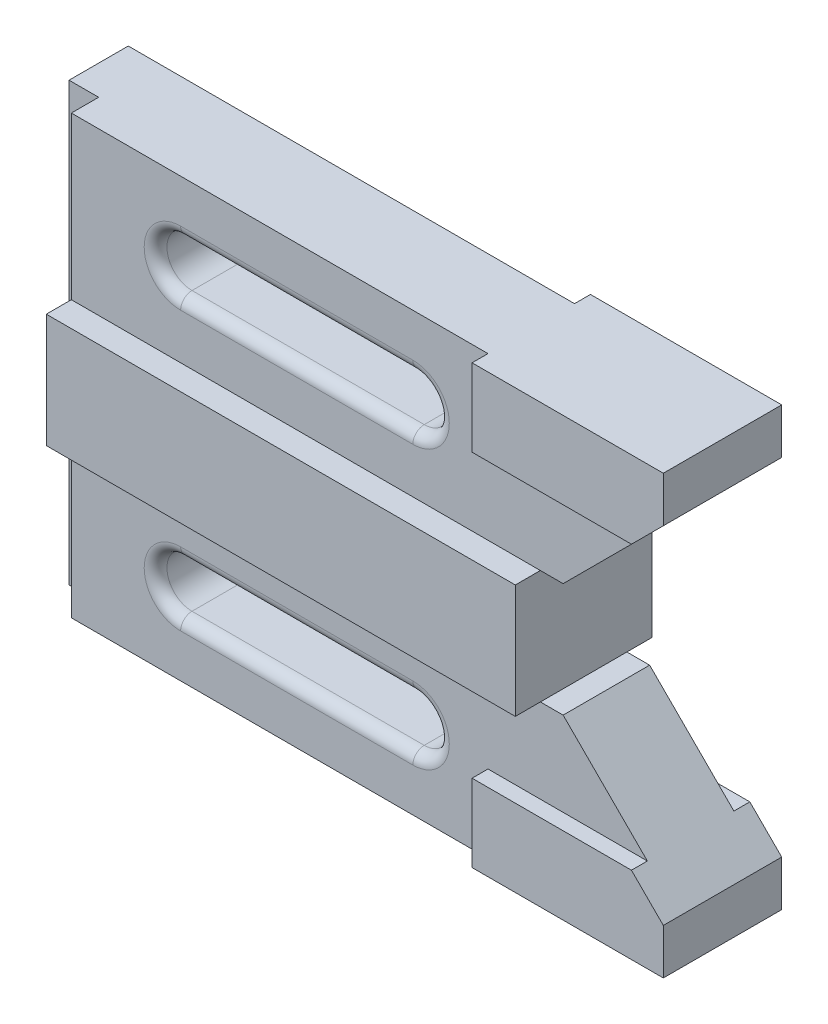
SolidWorks part; units mm, degrees
material "1060 Alloy"
ref_plane "Front Plane" through (0, 0, 0) normal (0, 0, 1) x (1, 0, 0)
ref_plane "Top Plane" through (0, 0, 0) normal (0, 1, 0) x (1, 0, 0)
ref_plane "Right Plane" through (0, 0, 0) normal (1, 0, 0) x (0, 0, -1)
sketch "Sketch1" plane through (0, 0, 0) normal (0, 0, 1) x (1, 0, 0)
  line L0 (58.7138, 0) -> (-58.7138, 0) construction
  line L1 (109.5, 0) -> (0, 0)
  line L2 (0, 0) -> (0, 48)
  line L3 (0, 48) -> (140, 48)
  line L4 (140, 48) -> (140, 38)
  line L5 (140, 38) -> (114.5, 12.5)
  line L6 (114.5, 12.5) -> (109.5, 12.5)
  line L7 (109.5, 12.5) -> (109.5, 0)
  line L8 (98, 48) -> (98, 31)
  line L9 (98, 31) -> (133, 31)
  line L10 (109.5, 12.5) -> (0, 12.5)
  line L11 (0, 30.5) -> (132.5, 30.5) construction
  line L12 (30.5, 48) -> (30.5, 0) construction
  line L13 (30.5, 30.5) -> (81.5, 30.5) construction
  line L14 (30.5, 36) -> (81.5, 36)
  line L15 (30.5, 25) -> (81.5, 25)
  arc A0 (30.5, 36) -> (30.5, 25) centre (30.5, 30.5) ccw
  arc A1 (81.5, 25) -> (81.5, 36) centre (81.5, 30.5) ccw
  point P4 (0, 0)
  point P21 (56, 30.5)
  dimension "D12" = 5.5
  dimension "D1" = 140
  dimension "D2" = 48
  dimension "D3" = 10
  dimension "D4" = 35.5
  dimension "D5" = 45
  dimension "D6" = 30.5
  dimension "D7" = 17
  dimension "D8" = 35
  dimension "D9" = 17.5
  dimension "D10" = 30.5
  dimension "D11" = 51
extrude "Boss-Extrude1" add sketch "Sketch1" along normal mid plane 30 contours L7 L10 L2 L1 region at (54.75, 6.25, 0)
extrude "Boss-Extrude2" add sketch "Sketch1<3>" along normal mid plane 19 contours L10 L6 L5 L9 L8 L3 L2 A1 L15 A0 L14 region at (54.75, 13.8766, 0)
sketch "Sketch1<3>" plane through (0, 0, 0) normal (0, 0, 1) x (1, 0, 0) same geometry as "Sketch1"
extrude "Boss-Extrude3" add sketch "Sketch1<4>" along normal mid plane 26 contours L8 L9 L5 L4 L3 region at (118.3367, 39.7191, 0)
sketch "Sketch1<4>" plane through (0, 0, 0) normal (0, 0, 1) x (1, 0, 0) same geometry as "Sketch1"
sketch "Sketch2" plane through (0, 48, 0) normal (0, 1, 0) x (1, 0, 0)
  line L0 (0, -9.5) -> (0, 9.5) construction
  line L1 (0, -3.5) -> (6.5, -3.5)
  line L2 (0, -3.5) -> (0, -15)
  line L3 (0, -15) -> (6.5, -15)
  line L4 (6.5, -3.5) -> (6.5, -15)
  line L5 (109.5, -15) -> (0, -15) construction
  dimension "D1" = 11.5
  dimension "D2" = 6.5
extrude "Cut-Extrude1" cut sketch "Sketch2" against normal through all
fillet "Fillet1" radius 2.5 8 edges at (25, 30.5, -9.5) (56, 25, -9.5) (87, 30.5, -9.5) (56, 36, -9.5) (87, 30.5, 9.5) (56, 25, 9.5) (25, 30.5, 9.5) (56, 36, 9.5)
mirror "Mirror2" about plane through (0, 0, 15) normal (0, -1, 0) of bodies 104
equation "\"A\" = 140mm"
equation "\"B\"= 51mm"
equation "\"C\"= 45deg"
equation "\"D1@Sketch1\"=\"A\""
equation "\"D5@Sketch1\"=\"C\""
equation "\"D11@Sketch1\"=\"B\""
